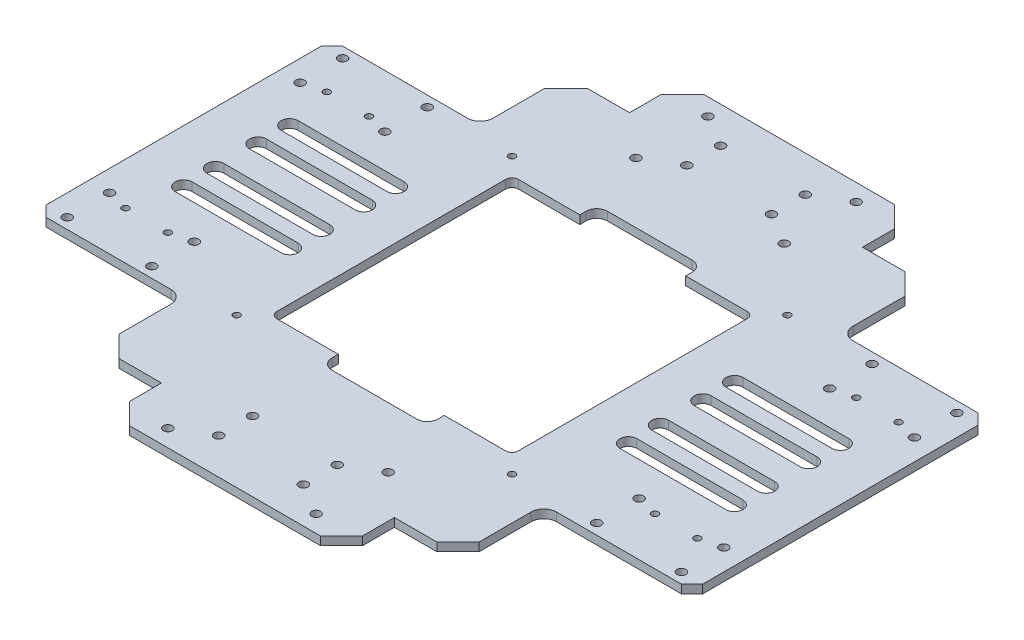
SolidWorks part; units mm, degrees
material "6061 Alloy"
ref_plane "前视基准面" through (0, 0, 0) normal (0, 0, 1) x (1, 0, 0)
ref_plane "上视基准面" through (0, 0, 0) normal (0, 1, 0) x (1, 0, 0)
ref_plane "右视基准面" through (0, 0, 0) normal (1, 0, 0) x (0, 0, -1)
sketch "草图1" plane through (0, 0, 0) normal (0, 1, 0) x (1, 0, 0)
  line L0 (-55, 135.4999) -> (-55, -135.4999)
  line L1 (-55, -135.4999) -> (55, -135.4999)
  line L2 (55, -135.4999) -> (55, 135.4999)
  line L3 (55, 135.4999) -> (-55, 135.4999)
  circle A0 centre (-35, 127.4999) radius 2.1
  circle A1 centre (-20, 118.4999) radius 2.1
  circle A2 centre (20, 118.4999) radius 2.1
  circle A3 centre (35, 127.4999) radius 2.1
  circle A4 centre (20, 102.4999) radius 2.1
  circle A5 centre (35, 93.4999) radius 2.1
  circle A6 centre (-35, 93.4999) radius 2.1
  circle A7 centre (-20, 102.4999) radius 2.1
  circle A8 centre (-35, -127.4999) radius 2.1
  circle A9 centre (-20, -118.4999) radius 2.1
  circle A10 centre (-20, -102.4999) radius 2.1
  circle A11 centre (20, -118.4999) radius 2.1
  circle A12 centre (20, -102.4999) radius 2.1
  circle A13 centre (35, -93.4999) radius 2.1
  circle A14 centre (35, -127.4999) radius 2.1
extrude "凸台-拉伸1" add sketch "草图1" along normal blind 4
chamfer "倒角1" distance 10 angle 45 4 edges at (-55, 2, 135.4999) (55, 2, 135.4999) (55, 2, -135.4999) (-55, 2, -135.4999)
sketch "草图2" plane through (0, 4, 0) normal (0, 1, 0) x (1, 0, 0)
  line L0 (-25, 45) -> (-40, 30)
  line L1 (-25, -65) -> (25, -65)
  line L2 (-25, -65) -> (-25, -45)
  line L3 (-25, 65) -> (25, 65)
  line L4 (25, -65) -> (25, -45)
  line L5 (-25, -65) -> (25, 65) construction
  line L6 (-25, 65) -> (25, -65) construction
  line L7 (-40, 30) -> (-40, -30)
  line L8 (25, 45) -> (25, 65)
  line L9 (-25, 45) -> (-25, 65)
  line L10 (0, 65) -> (0, -65) construction
  line L11 (25, 0) -> (-25, 0) construction
  line L13 (25, 45) -> (40, 30)
  line L14 (40, 30) -> (40, -30)
  line L15 (25, -45) -> (40, -30)
  line L16 (-25, -45) -> (-40, -30)
  point P0 (0, 0)
  dimension "D1" = 130
  dimension "D2" = 50
  dimension "D5" = 20
extrude "切除-拉伸1" cut sketch "草图2" against normal blind 4
fillet "圆角1" radius 5 4 edges at (-25, 2, 65) (25, 2, 65) (25, 2, -65) (-25, 2, -65)
sketch "草图3" plane through (0, 4, 0) normal (0, 1, 0) x (1, 0, 0)
  line L0 (55, 110.4999) -> (85, 110.4999)
  line L1 (-55, 125.4999) -> (-55, -125.4999) construction
  line L2 (-85, 93.4999) -> (-85, -102.4999)
  line L3 (55, -102.4999) -> (55, 93.4999)
  line L4 (-55, -102.4999) -> (-55, 93.4999)
  line L5 (0, 135.4999) -> (0, -135.4999) construction
  line L6 (45, 135.4999) -> (-45, 135.4999) construction
  line L7 (-45, -135.4999) -> (45, -135.4999) construction
  line L10 (85, 93.4999) -> (85, -102.4999)
  line L12 (55, -125.4999) -> (55, 125.4999) construction
  line L13 (-55, 110.4999) -> (-85, 110.4999)
  line L14 (-85, 110.4999) -> (-85, 93.4999)
  line L15 (-55, 93.4999) -> (-55, 110.4999)
  line L16 (85, 110.4999) -> (85, 93.4999)
  line L17 (55, 110.4999) -> (55, 93.4999)
  line L20 (-55, -110.4999) -> (-85, -110.4999)
  line L21 (-85, -110.4999) -> (-85, -102.4999)
  line L22 (-55, -102.4999) -> (-55, -110.4999)
  line L23 (85, -102.4999) -> (85, -110.4999)
  line L24 (85, -110.4999) -> (55, -110.4999)
  line L25 (55, -110.4999) -> (55, -102.4999)
extrude "凸台-拉伸2" add sketch "草图3" against normal blind 4
chamfer "倒角2" distance 10 angle 45 4 edges at (-85, 2, 110.4999) (85, 2, 110.4999) (85, 2, -110.4999) (-85, 2, -110.4999)
fillet "圆角3" radius 5 4 edges at (-40, 2, 30) (40, 2, 30) (40, 2, -30) (-40, 2, -30)
sketch "草图5" plane through (0, 4, 0) normal (0, 1, 0) x (1, 0, 0)
  line L1 (-65, -65) -> (65, -65) construction
  line L2 (-65, -65) -> (-65, 65) construction
  line L3 (-65, 65) -> (65, 65) construction
  line L4 (65, -65) -> (65, 65) construction
  line L5 (-65, -65) -> (65, 65) construction
  line L6 (-65, 65) -> (65, -65) construction
  circle A0 centre (-65, 65) radius 1.6
  circle A1 centre (65, 65) radius 1.6
  circle A2 centre (65, -65) radius 1.6
  circle A3 centre (-65, -65) radius 1.6
  point P0 (0, 0)
  dimension "D1" = 130
  dimension "D2" = 130
extrude "切除-拉伸2" cut sketch "草图5" against normal blind 4
sketch "草图7" plane through (0, 4, 0) normal (0, 1, 0) x (1, 0, 0)
  line L0 (-85, 0) -> (-85, 70)
  line L1 (-85, 100.4999) -> (-85, -100.4999) construction
  line L2 (-85, 70) -> (-155, 70)
  line L3 (-155, 70) -> (-155, -70)
  line L4 (-155, -70) -> (-85, -70)
  line L5 (-85, -70) -> (-85, 0)
  line L6 (85, 70) -> (155, 70)
  line L7 (85, -100.4999) -> (85, 100.4999) construction
  line L8 (155, 70) -> (155, -70)
  line L9 (155, -70) -> (85, -70)
  line L10 (85, -70) -> (85, 70)
extrude "凸台-拉伸3" add sketch "草图7" against normal blind 4
fillet "圆角4" radius 6 4 edges
sketch "草图8" plane through (0, 4, 0) normal (0, 1, 0) x (1, 0, 0)
  line L0 (0, 135.4999) -> (0, 0) construction
  circle A0 centre (105, 65) radius 2.1
  circle A1 centre (145, 65) radius 2.1
  circle A2 centre (145, 45) radius 2.1
  circle A3 centre (105, 45) radius 2.1
  circle A4 centre (145, -45) radius 2.1
  circle A5 centre (145, -65) radius 2.1
  circle A6 centre (105, -65) radius 2.1
  circle A7 centre (105, -45) radius 2.1
  circle A8 centre (-145, 65) radius 2.1
  circle A9 centre (-105, 65) radius 2.1
  circle A10 centre (-105, 45) radius 2.1
  circle A11 centre (-145, 45) radius 2.1
  circle A12 centre (-145, -45) radius 2.1
  circle A13 centre (-105, -45) radius 2.1
  circle A14 centre (-105, -65) radius 2.1
  circle A15 centre (-145, -65) radius 2.1
extrude "切除-拉伸3" cut sketch "草图8" against normal blind 4
sketch "草图9" plane through (0, 4, 0) normal (0, 1, 0) x (1, 0, 0)
  line L0 (-105, 42.9) -> (-105, 25.0287) construction
  line L1 (-130, 25.0287) -> (-80, 25.0287) construction
  line L2 (-130, 29.0287) -> (-80, 29.0287)
  line L3 (-130, 21.0287) -> (-80, 21.0287)
  line L4 (-130, 10.0287) -> (-80, 10.0287) construction
  line L5 (-130, 14.0287) -> (-80, 14.0287)
  line L6 (-130, 6.0287) -> (-80, 6.0287)
  line L7 (-155, 0) -> (0, 0) construction
  line L8 (-155, 70) -> (-155, -70) construction
  line L9 (0, 0) -> (0, 135.4999) construction
  line L10 (45, 135.4999) -> (-45, 135.4999) construction
  line L11 (-130, -25.0287) -> (-80, -25.0287) construction
  line L12 (-130, -29.0287) -> (-80, -29.0287)
  line L13 (-130, -21.0287) -> (-80, -21.0287)
  line L14 (-130, -10.0287) -> (-80, -10.0287) construction
  line L15 (-130, -14.0287) -> (-80, -14.0287)
  line L16 (-130, -6.0287) -> (-80, -6.0287)
  line L17 (130, 25.0287) -> (80, 25.0287) construction
  line L18 (130, 29.0287) -> (80, 29.0287)
  line L19 (130, 21.0287) -> (80, 21.0287)
  line L20 (130, 10.0287) -> (80, 10.0287) construction
  line L21 (130, 14.0287) -> (80, 14.0287)
  line L22 (130, 6.0287) -> (80, 6.0287)
  line L23 (130, -25.0287) -> (80, -25.0287) construction
  line L24 (130, -29.0287) -> (80, -29.0287)
  line L25 (130, -21.0287) -> (80, -21.0287)
  line L26 (130, -10.0287) -> (80, -10.0287) construction
  line L27 (130, -14.0287) -> (80, -14.0287)
  line L28 (130, -6.0287) -> (80, -6.0287)
  line L29 (-145, 45) -> (-145, 47.5) construction
  line L30 (-145, 47.5) -> (-105, 47.5) construction
  line L31 (-105, 47.5) -> (-105, 45) construction
  line L32 (-125, 47.5) -> (-125, 56.2221) construction
  line L33 (-125, -47.5) -> (-125, -56.2221) construction
  line L34 (-105, -47.5) -> (-105, -45) construction
  line L35 (-145, -47.5) -> (-105, -47.5) construction
  line L36 (-145, -45) -> (-145, -47.5) construction
  line L37 (145, -45) -> (145, -47.5) construction
  line L38 (145, -47.5) -> (105, -47.5) construction
  line L39 (105, -47.5) -> (105, -45) construction
  line L40 (125, -47.5) -> (125, -56.2221) construction
  line L41 (125, 47.5) -> (125, 56.2221) construction
  line L42 (105, 47.5) -> (105, 45) construction
  line L43 (145, 47.5) -> (105, 47.5) construction
  line L44 (145, 45) -> (145, 47.5) construction
  circle A0 centre (-105, 45) radius 2.1 construction
  arc A1 (-130, 29.0287) -> (-130, 21.0287) centre (-130, 25.0287) ccw
  arc A2 (-80, 21.0287) -> (-80, 29.0287) centre (-80, 25.0287) ccw
  arc A3 (-130, 14.0287) -> (-130, 6.0287) centre (-130, 10.0287) ccw
  arc A4 (-80, 6.0287) -> (-80, 14.0287) centre (-80, 10.0287) ccw
  arc A5 (-130, -29.0287) -> (-130, -21.0287) centre (-130, -25.0287) cw
  arc A6 (-80, -21.0287) -> (-80, -29.0287) centre (-80, -25.0287) cw
  arc A7 (-130, -14.0287) -> (-130, -6.0287) centre (-130, -10.0287) cw
  arc A8 (-80, -6.0287) -> (-80, -14.0287) centre (-80, -10.0287) cw
  arc A9 (130, 29.0287) -> (130, 21.0287) centre (130, 25.0287) cw
  arc A10 (80, 21.0287) -> (80, 29.0287) centre (80, 25.0287) cw
  arc A11 (130, 14.0287) -> (130, 6.0287) centre (130, 10.0287) cw
  arc A12 (80, 6.0287) -> (80, 14.0287) centre (80, 10.0287) cw
  arc A13 (130, -29.0287) -> (130, -21.0287) centre (130, -25.0287) ccw
  arc A14 (80, -21.0287) -> (80, -29.0287) centre (80, -25.0287) ccw
  arc A15 (130, -14.0287) -> (130, -6.0287) centre (130, -10.0287) ccw
  arc A16 (80, -6.0287) -> (80, -14.0287) centre (80, -10.0287) ccw
  circle A17 centre (-135, 47.5) radius 1.6
  circle A18 centre (-115, 47.5) radius 1.6
  circle A19 centre (-115, -47.5) radius 1.6
  circle A20 centre (-135, -47.5) radius 1.6
  circle A21 centre (135, -47.5) radius 1.6
  circle A22 centre (115, -47.5) radius 1.6
  circle A23 centre (115, 47.5) radius 1.6
  circle A24 centre (135, 47.5) radius 1.6
  point P7 (-105, 25.0287)
  point P15 (-105, 10.0287)
  point P29 (-105, -25.0287)
  point P36 (-105, -10.0287)
  point P43 (105, 25.0287)
  point P50 (105, 10.0287)
  point P57 (105, -25.0287)
  point P64 (105, -10.0287)
  dimension "D1" = 4
  dimension "D4" = 10
  dimension "D2" = 50
  dimension "D3" = 2
extrude "切除-拉伸4" cut sketch "草图9" against normal blind 4
chamfer "倒角3" distance 5 angle 45 4 edges at (155, 2, -70) (155, 2, 70) (-155, 2, 70) (-155, 2, -70)
sketch "草图11" plane through (0, 4, 0) normal (0, 1, 0) x (1, 0, 0)
  line L0 (-55, 55.0142) -> (55, 55.0142) construction
  line L1 (-55, 55.0142) -> (-55, -55.0142) construction
  line L2 (-55, -55.0142) -> (55, -55.0142) construction
  line L3 (55, 55.0142) -> (55, -55.0142) construction
  line L4 (-55, 55.0142) -> (55, -55.0142) construction
  line L5 (-55, -55.0142) -> (55, 55.0142) construction
  line L6 (-57, 57.0142) -> (57, 57.0142)
  line L7 (57, 57.0142) -> (57, -57.0142)
  line L8 (-57, -57.0142) -> (57, -57.0142)
  line L9 (-57, 57.0142) -> (-57, -57.0142)
  point P0 (0, 0)
  dimension "D1" = 2
extrude "切除-拉伸5" cut sketch "草图11" against normal blind 10
fillet "圆角5" radius 3 4 edges at (-57, 2, 57.0142) (57, 2, 57.0142) (57, 2, -57.0142) (-57, 2, -57.0142)
